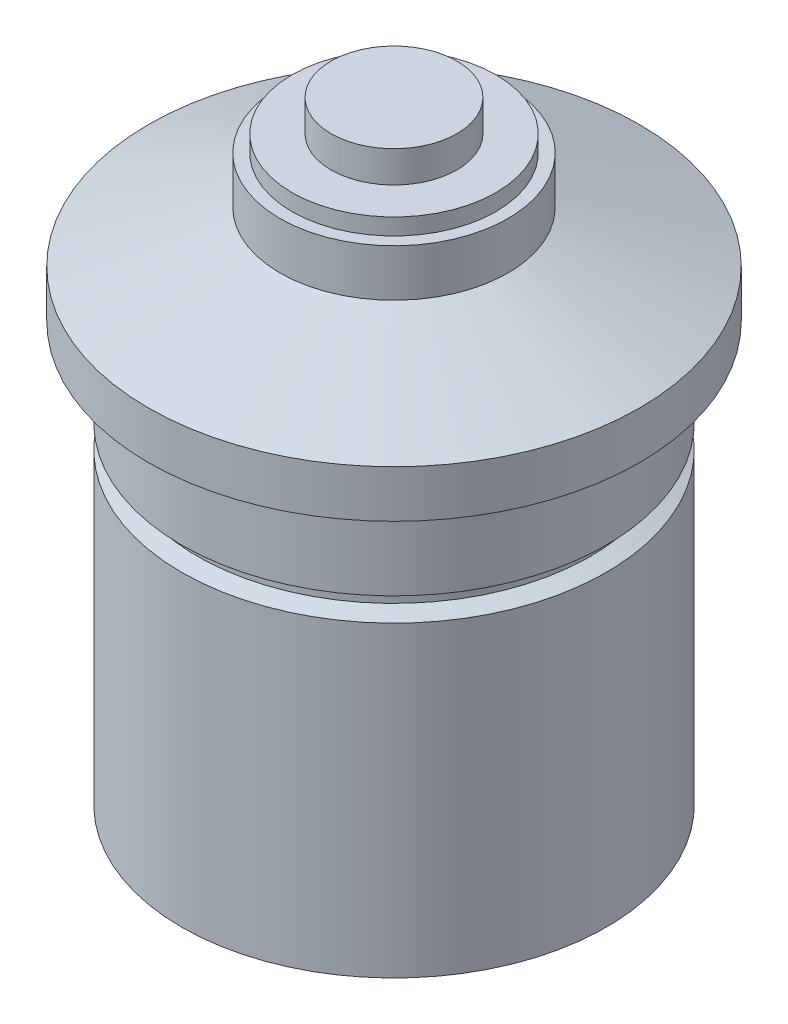
SolidWorks part; units mm, degrees
material "PET"
ref_plane "Front" through (0, 0, 0) normal (0, 0, 1) x (1, 0, 0)
ref_plane "Top" through (0, 0, 0) normal (0, 1, 0) x (1, 0, 0)
ref_plane "Right" through (0, 0, 0) normal (1, 0, 0) x (0, 0, -1)
ref_axis "Axis1" through (0, 0, 55) along (0, 0, -1)
sketch "Sketch1" plane through (0, 0, 0) normal (0, 0, 1) x (1, 0, 0)
  line L0 (0, 0) -> (0, 39.7) construction
  line L1 (0, 39.7) -> (7.25, 39.7) construction
  line L4 (4, 42.748) -> (0, 42.748)
  line L5 (0, 42.748) -> (0, 0)
  line L6 (7.25, 39.7) -> (7.25, 36.7)
  line L7 (7.25, 36.7) -> (15.6125, 33.447)
  line L8 (15.6125, 33.447) -> (15.6125, 30.4402)
  line L9 (15.6125, 30.4402) -> (13.5, 30.4402)
  line L10 (13.5, 30.4402) -> (13.5, 3.8)
  line L11 (13.5, 3.8) -> (9, 3.8)
  line L12 (9, 3.8) -> (9, 2.8)
  line L13 (9, 2.8) -> (7.71, 2.8)
  line L14 (7.71, 2.8) -> (7.71, 0)
  line L15 (7.71, 0) -> (0, 0)
  line L16 (7.25, 36.7) -> (7.25, 39.7)
  line L17 (4, 40.748) -> (6.488, 40.748)
  line L18 (4, 40.748) -> (4, 42.748)
  line L19 (6.488, 40.748) -> (6.488, 39.7)
  line L20 (6.488, 39.7) -> (7.25, 39.7)
  dimension "D1" = 39.7
  dimension "D2" = 7.71
  dimension "D3" = 13.5
  dimension "D4" = 15.6125
  dimension "D5" = 32.9
  dimension "D6" = 7.25
  dimension "D7" = 3
  dimension "D8" = 3.048
  dimension "D9" = 2
  dimension "D10" = 4
  dimension "D11" = 1
  dimension "D12" = 9
  dimension "D13" = 0.762
  dimension "D14" = 3.0068
  dimension "D15" = 6.2598
revolve "Revolve1" add sketch "Sketch1" angle 360 about L5 region at (6.3743, 20.4572, 0)
sketch "Sketch2" plane through (0, 0, 0) normal (0, 0, 1) x (1, 0, 0)
  line L0 (0, 0) -> (0, 42.748) construction
  line L1 (-7.71, 0) -> (7.71, 0) construction
  line L2 (4, 42.748) -> (-4, 42.748) construction
  line L3 (-13.5, 24.0902) -> (13.5, 24.0902) construction
  line L4 (-13.5, 30.4402) -> (-13.5, 3.8) construction
  line L5 (13.5, 3.8) -> (13.5, 30.4402) construction
  line L6 (-13.5, 30.4402) -> (13.5, 30.4402) construction
  line L7 (-13.5, 24.8402) -> (-13.5, 23.3402) construction
  line L8 (-13.5, 24.8402) -> (-12.484, 24.4712)
  line L9 (-12.484, 24.4712) -> (-12.484, 23.7092)
  line L10 (-12.484, 23.7092) -> (-13.5, 23.3402)
  arc A0 (-13.5, 24.8402) -> (-13.5, 23.3402) centre (-13.662, 24.0902) ccw
  point P12 (0, 24.0902)
  point P18 (-13.5, 24.0902)
  point P21 (-12.484, 24.0902)
  dimension "D5" = 0.7673
  dimension "D1" = 6.35
  dimension "D2" = 1.5
  dimension "D3" = 1.016
  dimension "D4" = 0.762
revolve "Cut-Revolve1" cut sketch "Sketch2" angle 360 about L0
fillet "Fillet1" radius 0.508 1 edges at (0, 2.8, 9)
